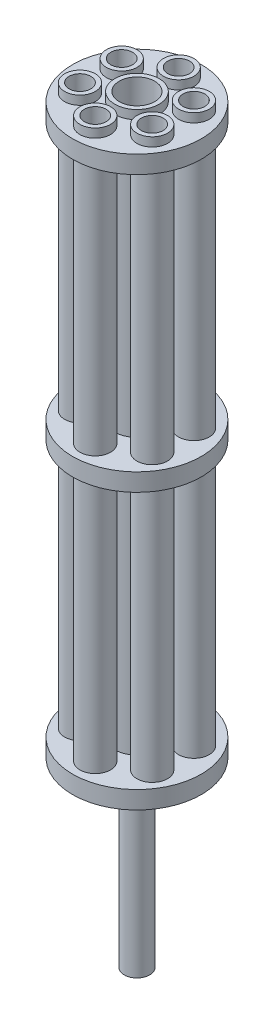
SolidWorks part; units mm, degrees
other "Markup1"
sketch "Sketch5" plane through (-15, 6, 15) normal (0, 1, 0) x (-1, 0, 0)
ref_plane "Front Plane" through (0, 0, 0) normal (0, 0, 1) x (1, 0, 0)
ref_plane "Top Plane" through (0, 0, 0) normal (0, 1, 0) x (1, 0, 0)
ref_plane "Right Plane" through (0, 0, 0) normal (1, 0, 0) x (0, 0, -1)
sketch "Sketch1" plane through (0, 0, 0) normal (0, 1, 0) x (1, 0, 0)
  circle A15 centre (0, 0) radius 14.5
  dimension "D1" = 29
extrude "Boss-Extrude1" add sketch "Sketch1" along normal blind 4
sketch "Sketch2" plane through (0, 4, 0) normal (0, 1, 0) x (1, 0, 0)
  line L0 (0, 0) -> (0, 9.4) construction
  line L1 (0, 0) -> (-8.1406, 4.7) construction
  line L2 (0, 0) -> (-8.1406, -4.7) construction
  line L3 (0, 9.4) -> (-8.1406, 4.7) construction
  line L4 (0, 0) -> (-2.4329, 9.0797) construction
  line L6 (0, 0) -> (-7.25, 12.5574) construction
  circle A0 centre (0, 0) radius 5
  circle A1 centre (0, 9.4) radius 3.4539
  circle A2 centre (8.1406, 4.7) radius 3.4539
  circle A3 centre (8.1406, -4.7) radius 3.4539
  circle A4 centre (0, -9.4) radius 3.4539
  circle A5 centre (-8.1406, -4.7) radius 3.4539
  circle A6 centre (-8.1406, 4.7) radius 3.4539
  circle A7 centre (0, 0) radius 4
  circle A8 centre (-8.1406, 4.7) radius 2.4539
  circle A9 centre (0, 9.4) radius 2.4539
  circle A10 centre (8.1406, 4.7) radius 2.4539
  circle A11 centre (8.1406, -4.7) radius 2.4539
  circle A12 centre (0, -9.4) radius 2.4539
  circle A13 centre (-8.1406, -4.7) radius 2.4539
  circle A14 centre (0, 0) radius 9.4 construction
  circle A15 centre (0, 0) radius 14.5 construction
  arc A16 (-6.6468, 6.6468) -> (-2.4329, 9.0797) centre (0, 0) cw construction
  arc A17 (6.6468, 6.6468) -> (9.0797, 2.4329) centre (0, 0) cw construction
  arc A18 (6.6468, 6.6468) -> (9.0797, 2.4329) centre (0, 0) cw construction
  point P17 (0, 0)
  point P31 (-6.0155, 5.9269)
  point P32 (-2.1251, 8.1731)
  point P33 (-2.4329, 9.0797)
  point P34 (-6.6468, 6.6468)
  dimension "D1" = 10
  dimension "D2" = 15
  dimension "D7" = 1
  dimension "D3" = 9.4
  dimension "D5" = 30
  dimension "D6" = 6
extrude "Boss-Extrude2" add sketch "Sketch2" along normal blind 2 and the other way blind 125
pattern_linear "LPattern4" count 3 spacing 62 along (0, -1, 0) of "Boss-Extrude1"
sketch "Sketch3" plane through (0, 4, 0) normal (0, 1, 0) x (1, 0, 0)
  circle A0 centre (0, 9.4) radius 2.4539 construction
  circle A1 centre (0, 0) radius 4
  circle A2 centre (0, 0) radius 4
  circle A3 centre (-8.1406, 4.7) radius 2.4539 construction
  circle A4 centre (-8.1406, -4.7) radius 2.4539 construction
  circle A5 centre (0, -9.4) radius 2.4539 construction
  circle A6 centre (8.1406, -4.7) radius 2.4539 construction
  circle A7 centre (8.1406, 4.7) radius 2.4539 construction
  circle A8 centre (0, 9.4) radius 2.4539
  circle A9 centre (-8.1406, 4.7) radius 2.4539
  circle A10 centre (-8.1406, -4.7) radius 2.4539
  circle A11 centre (0, -9.4) radius 2.4539
  circle A12 centre (8.1406, -4.7) radius 2.4539
  circle A13 centre (8.1406, 4.7) radius 2.4539
  dimension "D1" = 0
extrude "Cut-Extrude1" [suppressed] cut sketch "Sketch3" against normal through all
sketch "Sketch4" plane through (0, -124, 0) normal (0, -1, 0) x (1, 0, 0)
  circle A0 centre (0, 0) radius 5.2
  dimension "D1" = 10.4
extrude "Cut-Extrude2" [suppressed] cut sketch "Sketch4" against normal offset from surface (58 mm away) 4 up to face at (-8.1406, 4, -1.2461)
sketch "Sketch6" plane through (0, -124, 0) normal (0, -1, 0) x (1, 0, 0)
  line L0 (-16.7447, 7) -> (-12.6984, 7) construction
  line L1 (-16.7447, 7) -> (-16.7447, 3) construction
  line L2 (-16.7447, 3) -> (-16.7447, 0) construction
  line L3 (-16.7447, 0) -> (-19.7447, 0) construction
  line L4 (-19.7447, 0) -> (0, 0) construction
  line L5 (0, 0) -> (0, 14.5) construction
  arc A0 (-13.874, 4.2145) -> (-16.7447, 3) centre (-16.7447, 7) cw
  arc A2 (-16.7447, 3) -> (-16.7447, -3) centre (-16.7447, 0) ccw
  arc A3 (-13.874, -4.2145) -> (-16.7447, -3) centre (-16.7447, -7) ccw
  arc A4 (-13.874, 4.2145) -> (-13.874, -4.2145) centre (0, 0) ccw
  circle A5 centre (-16.7447, 0) radius 1.75
  circle A6 centre (0, 0) radius 14.5 construction
  point P21 (-19.7447, 0)
  dimension "D1" = 90
  dimension "D3" = 3
  dimension "D4" = 4
  dimension "D6" = 3.5
  dimension "D2" = 90
  dimension "D5" = 8.4291
extrude "Boss-Extrude3" [suppressed] add sketch "Sketch6" against normal up to surface (4 mm away)
mirror "Mirror1" [suppressed] about plane through (0, 0, 0) normal (1, 0, 0)
sketch "Sketch7" plane through (0, 0, 0) normal (1, 0, 0) x (0, 0, -1)
  line L1 (-14.5, -62) -> (14.5, -62)
  line L2 (-14.5, -62) -> (-14.5, -124)
  line L3 (-14.5, -124) -> (14.5, -124)
  line L4 (14.5, -62) -> (14.5, -124)
  line L6 (-14.5, -124) -> (14.5, -124) construction
extrude "Short Cut" [suppressed] cut sketch "Sketch7" against normal through all and the other way through all
sketch "Sketch8" plane through (0, 4, 0) normal (0, 1, 0) x (1, 0, 0)
  circle A0 centre (-8.1406, -4.7) radius 2.4539 construction
  circle A1 centre (0, -9.4) radius 2.4539 construction
  circle A2 centre (8.1406, -4.7) radius 2.4539 construction
  circle A3 centre (8.1406, 4.7) radius 2.4539 construction
  circle A4 centre (0, 9.4) radius 2.4539 construction
  circle A5 centre (-8.1406, 4.7) radius 2.4539 construction
  circle A6 centre (-8.1406, -4.7) radius 2.4539
  circle A7 centre (0, -9.4) radius 2.4539
  circle A8 centre (8.1406, -4.7) radius 2.4539
  circle A9 centre (8.1406, 4.7) radius 2.4539
  circle A10 centre (0, 9.4) radius 2.4539
  circle A11 centre (-8.1406, 4.7) radius 2.4539
extrude "Cut-Extrude4" cut sketch "Sketch8" against normal up to surface (128 mm away) up to face at (0, -124, 14.5)
sketch "Sketch12" plane through (0, -124, 0) normal (0, -1, 0) x (1, 0, 0)
  circle A0 centre (0, 0) radius 2.875
  dimension "D1" = 5.75
extrude "Boss-Extrude4" add sketch "Sketch12" along normal blind 41
sketch "Sketch9" plane through (0, -165, 0) normal (0, -1, 0) x (1, 0, 0)
  line L0 (1.5, 1.4697) -> (1.5, -1.4697)
  line L1 (-2.1, 1.9636) -> (-2.1, -1.9636) construction
  arc A0 (1.5, 1.4697) -> (1.5, -1.4697) centre (0, 0) ccw
  circle A1 centre (0, 0) radius 2.875 construction
  dimension "D1" = 4.2
  dimension "D2" = 3.6
extrude "Cut-Extrude5" cut sketch "Sketch9" against normal up to surface (41 mm away) up to face at (0, -124, 2.875)
sketch "Sketch14" plane through (0, 4, 0) normal (0, 1, 0) x (1, 0, 0)
  circle A1 centre (0, 0) radius 4
  circle A2 centre (0, 0) radius 4
  dimension "D1" = 0
extrude "Cut-Extrude6" cut sketch "Sketch14" against normal up to surface (124 mm away) up to face at (-8.1406, -120, 8.1539)
sketch "Sketch10" plane through (0, 0, 0) normal (1, 0, 0) x (0, 0, -1)
  line L0 (-14.5, 4) -> (-14.5, 0) construction
  line L1 (-14.5, 6) -> (14.5, 6)
  line L2 (-14.5, 6) -> (-14.5, -123)
  line L3 (-14.5, -123) -> (14.5, -123)
  line L4 (14.5, 6) -> (14.5, -123)
  line L5 (14.5, 0) -> (14.5, 4) construction
  line L6 (8.1539, 6) -> (1.2461, 6) construction
  line L7 (14.5, -123) -> (14.5, -124) construction
  dimension "D1" = 129
extrude "Short cut 2" [suppressed] cut sketch "Sketch10" against normal through all and the other way through all
sketch "Sketch15" plane through (0, 0, 0) normal (1, 0, 0) x (0, 0, -1)
  line L0 (-2.875, -124) -> (-2.875, -165) construction
  line L1 (-2.875, -132) -> (2.875, -132)
  line L2 (-2.875, -132) -> (-2.875, -165)
  line L3 (-2.875, -165) -> (2.875, -165)
  line L4 (2.875, -132) -> (2.875, -165)
  line L5 (-14.5, -124) -> (14.5, -124) construction
  dimension "D1" = 8
extrude "Short Cut 3" [suppressed] cut sketch "Sketch15" against normal through all both and the other way through all
